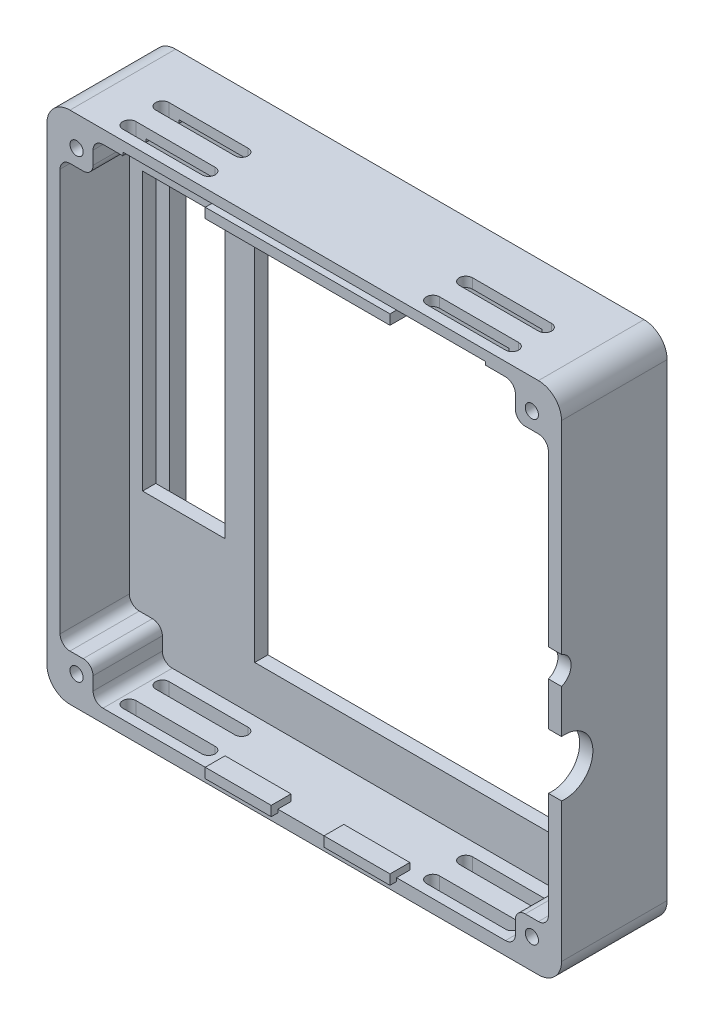
SolidWorks part; units mm, degrees
ref_plane "前视基准面" through (0, 0, 0) normal (0, 0, 1) x (1, 0, 0)
ref_plane "上视基准面" through (0, 0, 0) normal (0, 1, 0) x (1, 0, 0)
ref_plane "右视基准面" through (0, 0, 0) normal (1, 0, 0) x (0, 0, -1)
other "Configuration Table"
sketch "草图1" plane through (0, 0, 0) normal (0, 0, 1) x (1, 0, 0)
  line L1 (-39, -39) -> (39, -39)
  line L2 (-39, -39) -> (-39, 39)
  line L3 (-39, 39) -> (39, 39)
  line L4 (39, -39) -> (39, 39)
  line L5 (-39, -39) -> (39, 39) construction
  line L6 (-39, 39) -> (39, -39) construction
  point P0 (0, 0)
  dimension "D1" = 78
extrude "凸台-拉伸1" add sketch "草图1" along normal blind 5.5
sketch "草图2" plane through (0, 0, 5.5) normal (0, 0, 1) x (1, 0, 0)
  line L1 (-39, -39) -> (39, -39)
  line L2 (-39, -39) -> (-39, 39)
  line L3 (-39, 39) -> (39, 39)
  line L4 (39, -39) -> (39, 39)
  line L5 (-39, -39) -> (39, 39) construction
  line L6 (-39, 39) -> (39, -39) construction
  line L7 (37, 37) -> (-37, 37)
  line L8 (37, 37) -> (37, -37)
  line L9 (37, -37) -> (-37, -37)
  line L10 (-37, 37) -> (-37, -37)
  line L11 (37, 37) -> (-37, -37) construction
  line L12 (37, -37) -> (-37, 37) construction
  line L13 (-37, 37) -> (-32, 37)
  line L14 (-37, 37) -> (-37, 32)
  line L15 (-37, 32) -> (-32, 32)
  line L16 (-32, 37) -> (-32, 32)
  line L17 (37, 37) -> (32, 37)
  line L18 (37, 37) -> (37, 32)
  line L19 (37, 32) -> (32, 32)
  line L20 (32, 37) -> (32, 32)
  line L21 (-37, -37) -> (-32, -37)
  line L22 (-37, -37) -> (-37, -32)
  line L23 (-37, -32) -> (-32, -32)
  line L24 (-32, -37) -> (-32, -32)
  line L25 (37, -37) -> (32, -37)
  line L26 (37, -37) -> (37, -32)
  line L27 (37, -32) -> (32, -32)
  line L28 (32, -37) -> (32, -32)
  point P0 (0, 0)
  point P7 (0, 0)
  line M22 (39, -39) -> (39, 39)
  line M23 (39, 39) -> (-39, 39)
  line M24 (-39, 39) -> (-39, -39)
  line M25 (-39, -39) -> (39, -39)
  dimension "D1" = 2
  dimension "D2" = 5
extrude "凸台-拉伸2" add sketch "草图2" along normal blind 10.5 contours L10 L7 L8 L9 M25 M22 M23 M24 | L16 L7 L10 L15 | L7 L20 L19 L8 | L28 L9 L8 L27 | L9 L24 L23 L10 region at (-37.8969, 0, 5.5) region at (34.5, 34.5, 5.5) region at (-34.5, 34.5, 5.5) region at (34.5, -34.5, 5.5) region at (-34.5, -34.5, 5.5)
fillet "圆角1" radius 1.5 12 edges at (37, 32, 10.75) (32, 32, 10.75) (32, 37, 10.75) (37, -32, 10.75) (32, -32, 10.75) (32, -37, 10.75) (-32, -37, 10.75) (-32, -32, 10.75) (-37, -32, 10.75) (-37, 32, 10.75) (-32, 37, 10.75) (-32, 32, 10.75)
fillet "圆角2" radius 3.5 4 edges at (-39, 39, 8) (39, 39, 8) (39, -39, 8) (-39, -39, 8)
sketch "草图3" plane through (0, 0, 0) normal (0, 0, -1) x (-1, 0, 0)
  line L8 (37.5, -35.5) -> (37.5, 35.5)
  line L9 (-35.5, -37.5) -> (35.5, -37.5)
  line L10 (-37.5, 35.5) -> (-37.5, -35.5)
  line L11 (35.5, 37.5) -> (-35.5, 37.5)
  line L12 (37.5, -35.5) -> (37.5, 35.5)
  line L13 (-35.5, -37.5) -> (35.5, -37.5)
  line L14 (-37.5, 35.5) -> (-37.5, -35.5)
  line L15 (35.5, 37.5) -> (-35.5, 37.5)
  arc A8 (37.5, 35.5) -> (35.5, 37.5) centre (35.5, 35.5) ccw
  arc A9 (35.5, -37.5) -> (37.5, -35.5) centre (35.5, -35.5) ccw
  arc A10 (-37.5, -35.5) -> (-35.5, -37.5) centre (-35.5, -35.5) ccw
  arc A11 (-35.5, 37.5) -> (-37.5, 35.5) centre (-35.5, 35.5) ccw
  arc A12 (37.5, 35.5) -> (35.5, 37.5) centre (35.5, 35.5) ccw
  arc A13 (35.5, -37.5) -> (37.5, -35.5) centre (35.5, -35.5) ccw
  arc A14 (-37.5, -35.5) -> (-35.5, -37.5) centre (-35.5, -35.5) ccw
  arc A15 (-35.5, 37.5) -> (-37.5, 35.5) centre (-35.5, 35.5) ccw
  dimension "D1" = 1.5
extrude "切除-拉伸1" cut sketch "草图3" against normal blind 1
sketch "草图4" plane through (0, 0, 1) normal (0, 0, -1) x (-1, 0, 0)
  line L0 (35.5, 37.5) -> (-35.5, 37.5) construction
  line L1 (-32.95, 37.5) -> (32.95, 37.5)
  line L2 (-32.95, 37.5) -> (-32.95, -33)
  line L3 (-32.95, -33) -> (32.95, -33)
  line L4 (32.95, 37.5) -> (32.95, -33)
  line L6 (0, 0) -> (0, 26.6317) construction
  line L7 (-32.95, 36.85) -> (32.95, 36.85)
  line L8 (27.5, 36.85) -> (27.5, 37.5)
  line L9 (-27.5, 36.85) -> (-27.5, 37.5)
  line M10 (35.5, 37.5) -> (-35.5, 37.5)
  dimension "D1" = 70.5
  dimension "D2" = 65.9
  dimension "D3" = 0.65
  dimension "D4" = 55
extrude "切除-拉伸2" cut sketch "草图4" against normal blind 2.5 contours L3 L6 L7 L2 | L6 L3 L4 L7 | L7 L6 L9 M10 | L6 L7 L8 L1 region at (0, 37.175, 1) region at (30.225, 35.8897, 1)
sketch "草图5" plane through (0, 0, 1) normal (0, 0, -1) x (-1, 0, 0)
  line L0 (-35.5, 39) -> (35.5, 39) construction
  line L1 (-34.5, -34.5) -> (34.5, -34.5) construction
  line L2 (-34.5, -34.5) -> (-34.5, 34.5) construction
  line L3 (-34.5, 34.5) -> (34.5, 34.5) construction
  line L4 (34.5, -34.5) -> (34.5, 34.5) construction
  line L5 (-34.5, -34.5) -> (34.5, 34.5) construction
  line L6 (-34.5, 34.5) -> (34.5, -34.5) construction
  circle A0 centre (-34.5, 34.5) radius 1
  circle A1 centre (34.5, 34.5) radius 1
  circle A2 centre (34.5, -34.5) radius 1
  circle A3 centre (-34.5, -34.5) radius 1
  point P0 (0, 0)
  dimension "D2" = 2
  dimension "D1" = 4.5
extrude "切除-拉伸3" cut sketch "草图5" against normal through all
sketch "草图6" plane through (0, 0, 3.5) normal (0, 0, -1) x (-1, 0, 0)
  line L1 (-27.5, 37.5) -> (27.5, 37.5)
  line L2 (-27.5, 37.5) -> (-27.5, 35.5)
  line L3 (-27.5, 35.5) -> (27.5, 35.5)
  line L4 (27.5, 37.5) -> (27.5, 35.5)
  line L5 (-36, 28) -> (18, 28)
  line L6 (-36, 28) -> (-36, -30)
  line L7 (-36, -30) -> (18, -30)
  line L8 (18, 28) -> (18, -30)
  line L9 (22.5, 26) -> (35, 26)
  line L10 (22.5, 26) -> (22.5, -16)
  line L11 (22.5, -16) -> (35, -16)
  line L12 (35, 26) -> (35, -16)
  dimension "D1" = 2
  dimension "D2" = 54
  dimension "D3" = 30
  dimension "D4" = 58
  dimension "D5" = 36
  dimension "D6" = 22.5
  dimension "D7" = 12.5
  dimension "D8" = 42
  dimension "D9" = 16
extrude "切除-拉伸4" cut sketch "草图6" against normal through all
sketch "草图7" plane through (0, 0, 16) normal (0, 0, 1) x (1, 0, 0)
  line L0 (-15.0283, 0) -> (15.498, 0) construction
  line L17 (0, -8.9343) -> (0, 15.7561) construction
  line L20 (35.5, -37.5) -> (-35.5, -37.5) construction
  line L21 (14, -37.5) -> (4, -37.5)
  line L22 (14, -37.5) -> (14, -36)
  line L23 (14, -36) -> (4, -36)
  line L24 (4, -37.5) -> (4, -36)
  line L25 (-27.5, 37.5) -> (27.5, 37.5) construction
  line L26 (-4, -37.5) -> (-14, -37.5)
  line L27 (-4, -37.5) -> (-4, -36)
  line L28 (-4, -36) -> (-14, -36)
  line L29 (-14, -37.5) -> (-14, -36)
  line L30 (-14, 37.5) -> (14, 37.5)
  line L31 (-14, 37.5) -> (-14, 36)
  line L32 (-14, 36) -> (14, 36)
  line L33 (14, 37.5) -> (14, 36)
  dimension "D1" = 1.5
  dimension "D2" = 28
  dimension "D4" = 1.5
  dimension "D5" = 28
  dimension "D6" = 8
extrude "凸台-拉伸3" add sketch "草图7" along normal blind 1 and the other way blind 2
sketch "草图8" plane through (39, 0, 0) normal (1, 0, 0) x (0, 0, -1)
  line L0 (-16, -35.5) -> (0, -35.5) construction
  line L1 (-16, -35.5) -> (-16, 35.5) construction
  line L2 (-16, 4.8) -> (-16, 0.6) construction
  circle A0 centre (-15.5, -10.2) radius 4.25
  circle A1 centre (-16.8, 2.7) radius 2.2472
  dimension "D1" = 8.5
  dimension "D4" = 4.2
  dimension "D2" = 25.3
  dimension "D3" = 0.5
  dimension "D5" = 38.2
  dimension "D6" = 0.8
extrude "切除-拉伸5" cut sketch "草图8" against normal blind 10
sketch "草图9" plane through (0, -39, 0) normal (0, -1, 0) x (1, 0, 0)
  line L0 (-29, 13.5) -> (-17, 13.5) construction
  line L1 (-29, 14.5) -> (-17, 14.5)
  line L2 (-29, 12.5) -> (-17, 12.5)
  line L3 (-39, 0) -> (-39, 16) construction
  line L4 (-35.5, 16) -> (35.5, 16) construction
  line L5 (-29, 8.5) -> (-17, 8.5) construction
  line L6 (-29, 9.5) -> (-17, 9.5)
  line L7 (-29, 7.5) -> (-17, 7.5)
  line L8 (-29, 13.5) -> (-29, 8.5) construction
  line L9 (0, -1000) -> (0, 49000) construction
  line L11 (29, 8.5) -> (17, 8.5) construction
  line L12 (29, 9.5) -> (17, 9.5)
  line L13 (29, 7.5) -> (17, 7.5)
  line L14 (29, 13.5) -> (17, 13.5) construction
  line L15 (29, 14.5) -> (17, 14.5)
  line L16 (29, 12.5) -> (17, 12.5)
  arc A0 (-29, 14.5) -> (-29, 12.5) centre (-29, 13.5) ccw
  arc A1 (-17, 12.5) -> (-17, 14.5) centre (-17, 13.5) ccw
  arc A2 (-29, 9.5) -> (-29, 7.5) centre (-29, 8.5) ccw
  arc A3 (-17, 7.5) -> (-17, 9.5) centre (-17, 8.5) ccw
  arc A4 (29, 9.5) -> (29, 7.5) centre (29, 8.5) cw
  arc A5 (17, 7.5) -> (17, 9.5) centre (17, 8.5) cw
  arc A6 (29, 14.5) -> (29, 12.5) centre (29, 13.5) cw
  arc A7 (17, 12.5) -> (17, 14.5) centre (17, 13.5) cw
  point P2 (-23, 13.5)
  point P15 (-23, 8.5)
  point P27 (23, 8.5)
  point P34 (23, 13.5)
  dimension "D3" = 1
  dimension "D1" = 12
  dimension "D2" = 10
  dimension "D4" = 2.5
  dimension "D6" = 5
  dimension "D5" = 2
extrude "切除-拉伸6" cut sketch "草图9" against normal through all
